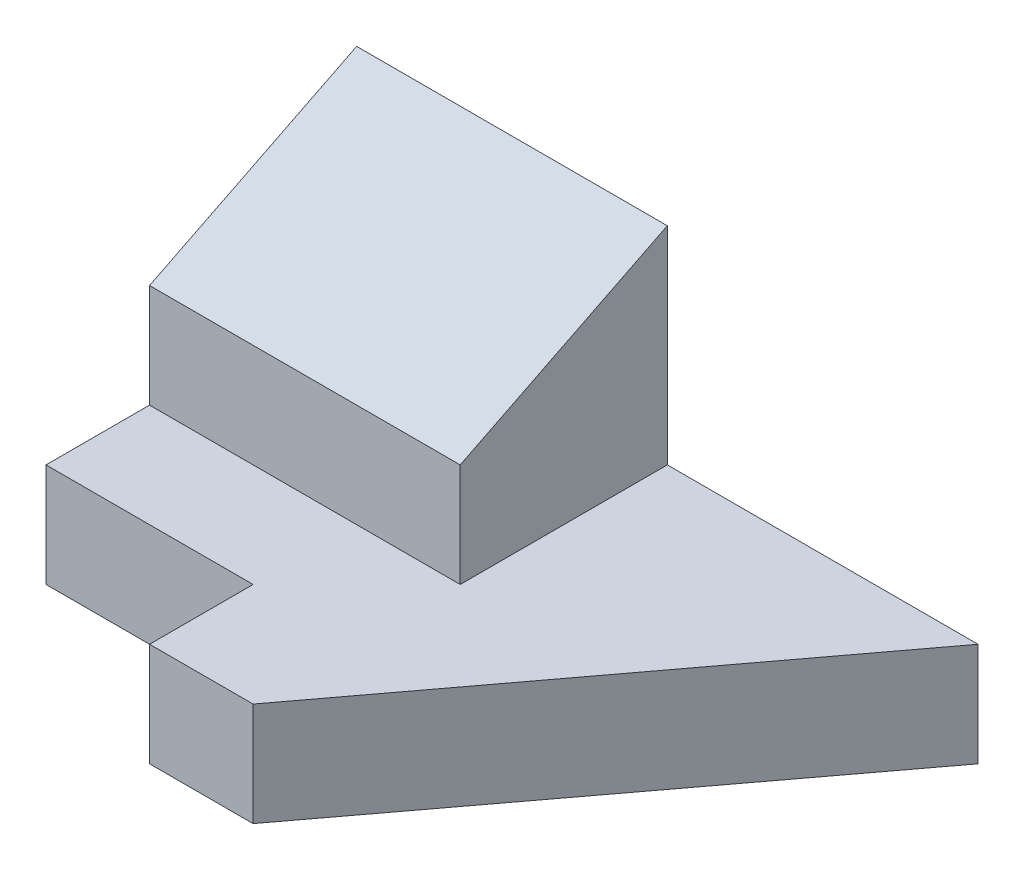
SolidWorks part; units mm, degrees
ref_plane "前基準面" through (0, 0, 0) normal (0, 0, 1) x (1, 0, 0)
ref_plane "上基準面" through (0, 0, 0) normal (0, 1, 0) x (1, 0, 0)
ref_plane "右基準面" through (0, 0, 0) normal (1, 0, 0) x (0, 0, -1)
sketch "草圖1" plane through (0, 0, 0) normal (0, 1, 0) x (1, 0, 0)
  line L0 (0, 41.9832) -> (0, -29.9162) construction
  line L1 (0, 0) -> (-60, 0)
  line L2 (-60, 0) -> (-60, -30)
  line L3 (-60, -30) -> (-40, -30)
  line L4 (-40, -30) -> (-40, -40)
  line L5 (-40, -40) -> (-30, -40)
  line L6 (-30, -40) -> (0, 0)
  line L7 (-60, -20) -> (-30, -20)
  line L8 (-30, -20) -> (-30, 0)
  dimension "D1" = 60
  dimension "D2" = 30
  dimension "D3" = 10
  dimension "D4" = 10
  dimension "D5" = 20
  dimension "D6" = 30
  dimension "D7" = 20
extrude "填料-伸長1" add sketch "草圖1" along normal blind 10 contours L8 L7 L2 L3 L4 L5 L6 L1 | L6 L1 L2 L3 L4 L5 region at (-29, 0, 19)
extrude "填料-伸長2" add sketch "草圖1<3>" along normal blind 30 contours L7 L8 L1 L2 region at (-45, 0, 10)
sketch "草圖1<3>" plane through (0, 0, 0) normal (0, 1, 0) x (1, 0, 0) same geometry as "草圖1"
sketch "草圖2" plane through (-30, 0, 0) normal (1, 0, 0) x (0, 0, -1)
  line L0 (0, 30) -> (-20, 20)
  line L1 (-20, 30) -> (-20, 10) construction
  line L2 (0, 30) -> (-20, 30)
  line L3 (-20, 30) -> (-20, 20)
extrude "除料-伸長1" cut sketch "草圖2" against normal blind 59
